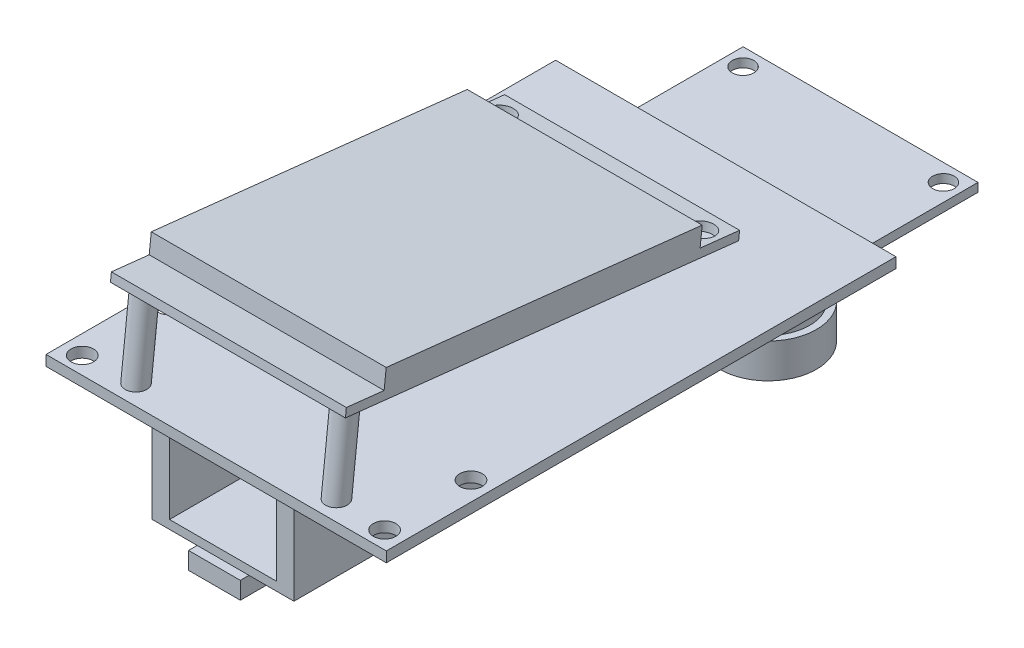
SolidWorks part; units mm, degrees
ref_plane "Front Plane" through (0, 0, 0) normal (0, 0, 1) x (1, 0, 0)
ref_plane "Top Plane" through (0, 0, 0) normal (0, 1, 0) x (1, 0, 0)
ref_plane "Right Plane" through (0, 0, 0) normal (1, 0, 0) x (0, 0, -1)
sketch "Sketch1" plane through (0, 0, 0) normal (0, 1, 0) x (1, 0, 0)
  line L0 (0, -46.1056) -> (0, 10.2781) construction
  line L1 (-25.019, 37.465) -> (25.019, 37.465)
  line L2 (-25.019, 37.465) -> (-25.019, -37.465)
  line L3 (-25.019, -37.465) -> (25.019, -37.465)
  line L4 (25.019, 37.465) -> (25.019, -37.465)
  circle A0 centre (22.225, -34.925) radius 1.651
  circle A1 centre (22.225, -22.225) radius 1.651
  circle A2 centre (-22.225, -34.925) radius 1.651
  circle A3 centre (-22.225, -22.225) radius 1.651
  point P4 (0, 37.465)
  point P6 (25.019, 0)
  point P12 (15.9217, -27.0723)
  point P16 (27.5932, -35.6314)
  dimension "D4" = 3.302
  dimension "D1" = 50.038
  dimension "D2" = 74.93
  dimension "D3" = 2.54
  dimension "D5" = 12.7
  dimension "D6" = 22.225
extrude "Boss-Extrude1" add sketch "Sketch1" along normal blind 1.524
sketch "Sketch2" plane through (0, 0, 0) normal (1, 0, 0) x (0, 0, -1)
  line L0 (22.0864, 7.366) -> (-35.732, 13.716)
  line L1 (22.0864, 7.366) -> (22.225, 8.6284)
  line L2 (-35.732, 13.716) -> (-35.5933, 14.9784)
  line L3 (22.225, 8.6284) -> (-35.5933, 14.9784)
  line L4 (37.465, 1.524) -> (37.465, 0) construction
  line L5 (-37.465, 1.524) -> (37.465, 1.524) construction
  line L6 (-30.0387, 14.3684) -> (16.4179, 9.2662)
  line L7 (-30.0387, 14.3684) -> (-29.7337, 17.1457)
  line L8 (16.4179, 9.2662) -> (16.7229, 12.0435)
  line L9 (-29.7337, 17.1457) -> (16.7229, 12.0435)
  dimension "D1" = 1.27
  dimension "D2" = 58.166
  dimension "D3" = 15.24
  dimension "D4" = 5.842
  dimension "D5" = 12.192
  dimension "D6" = 2.794
  dimension "D7" = 46.736
  dimension "D8" = 5.842
extrude "Boss-Extrude2" add sketch "Sketch2" along normal mid plane 34.544 separate body contours L9 L7 L3 L8 | L1 L3 L2 L0 region at (0, 11.1722, 6.7535) region at (0, 13.2059, 6.6579)
sketch "Sketch3" plane through (0, 10.9374, -1.2012) normal (0, 0.994, -0.1092) x (1, 0, 0)
  line L0 (-17.272, 21.1502) -> (-17.272, 15.3082) construction
  line L2 (17.272, 21.1502) -> (-17.272, 21.1502) construction
  line L3 (0, -9.4301) -> (0, 9.4301) construction
  circle A0 centre (-14.732, 18.1022) radius 1.778
  circle A2 centre (14.732, 18.1022) radius 1.778
  point P2 (0, 0)
  point P4 (0, 0)
  point P8 (-14.8989, 21.1502)
  dimension "D1" = 3.556
  dimension "D2" = 2.54
  dimension "D3" = 3.048
extrude "Cut-Extrude2" cut sketch "Sketch3" against normal up to next (1.27 mm away) contours A2 | A0 region at (14.732, 8.9612, -19.1952)
sketch "Sketch4" plane through (0, 9.675, -1.0626) normal (0, -0.994, 0.1092) x (1, 0, 0)
  line L0 (0.889, -19.3722) -> (-0.889, -19.3722) construction
  line L1 (17.272, -21.1502) -> (-17.272, -21.1502) construction
  line L2 (17.272, 31.4278) -> (17.272, 37.0158) construction
  line L4 (17.272, 37.0158) -> (-17.272, 37.0158) construction
  line L5 (0, -9.4301) -> (0, 9.4301) construction
  circle A0 centre (-0.889, -19.3722) radius 0.254
  circle A1 centre (0.889, -19.3722) radius 0.254
  circle A2 centre (-2.667, -19.3722) radius 0.254
  circle A3 centre (-4.445, -19.3722) radius 0.254
  circle A4 centre (-6.223, -19.3722) radius 0.254
  circle A5 centre (2.667, -19.3722) radius 0.254
  circle A6 centre (4.445, -19.3722) radius 0.254
  circle A7 centre (6.223, -19.3722) radius 0.254
  circle A8 centre (14.732, 34.4758) radius 1.5875
  circle A10 centre (-14.732, 34.4758) radius 1.5875
  point P8 (0, -19.3722)
  point P24 (0, 0)
  point P26 (14.0296, 37.0158)
  dimension "D1" = 0.508
  dimension "D2" = 0.508
  dimension "D7" = 3.175
  dimension "D3" = 1.778
  dimension "D4" = 1.778
  dimension "D8" = 2.54
  dimension "D9" = 2.54
  dimension "D5" = 4
  dimension "D6" = 4
extrude "Boss-Extrude3" add sketch "Sketch4" along normal up to next
sketch "Sketch5" plane through (0, 0, 0) normal (0, -1, 0) x (1, 0, 0)
  line L1 (10.414, 36.449) -> (7.874, 36.449)
  line L2 (10.414, 36.449) -> (10.414, -14.351)
  line L3 (10.414, -14.351) -> (7.874, -14.351)
  line L4 (7.874, 36.449) -> (7.874, -14.351)
  line L5 (-25.019, 37.465) -> (25.019, 37.465) construction
  line L6 (0, -9.4301) -> (0, 9.4301) construction
  line L7 (-10.414, -14.351) -> (-7.874, -14.351)
  line L8 (-7.874, 36.449) -> (-7.874, -14.351)
  line L9 (-10.414, 36.449) -> (-7.874, 36.449)
  line L10 (-10.414, 36.449) -> (-10.414, -14.351)
  point P4 (8.8726, -5.1163)
  dimension "D1" = 2.54
  dimension "D2" = 50.8
  dimension "D3" = 1.016
  dimension "D4" = 10.414
extrude "Boss-Extrude4" add sketch "Sketch5" along normal blind 11.43
sketch "Sketch6" plane through (0, -11.43, 0) normal (0, -1, 0) x (1, 0, 0)
  line L0 (-10.414, 36.449) -> (-10.414, -14.351) construction
  line L1 (-10.414, 36.449) -> (10.414, 36.449)
  line L2 (-10.414, 36.449) -> (-10.414, -14.351)
  line L3 (-10.414, -14.351) -> (10.414, -14.351)
  line L4 (10.414, 36.449) -> (10.414, -14.351)
  line L5 (-7.874, 36.449) -> (-10.414, 36.449) construction
extrude "Boss-Extrude5" add sketch "Sketch6" along normal blind 1.27
sketch "Sketch7" plane through (0, -12.7, 0) normal (0, -1, 0) x (1, 0, 0)
  line L1 (10.414, 36.449) -> (-10.414, 36.449) construction
  line L4 (-10.414, 36.449) -> (-10.414, -14.351) construction
  line L5 (0, -16.4151) -> (0, 16.4151) construction
  line L7 (3.81, 31.369) -> (-3.81, 31.369)
  line L8 (3.81, 31.369) -> (3.81, 37.719)
  line L9 (3.81, 37.719) -> (-3.81, 37.719)
  line L10 (-3.81, 31.369) -> (-3.81, 37.719)
  circle A0 centre (-9.144, 35.179) radius 0.889
  circle A1 centre (-9.144, 32.639) radius 0.889
  circle A2 centre (-9.144, 30.099) radius 0.889
  circle A3 centre (-9.144, 27.559) radius 0.889
  circle A4 centre (-9.144, 25.019) radius 0.889
  circle A5 centre (-9.144, 22.479) radius 0.889
  circle A6 centre (-9.144, 19.939) radius 0.889
  circle A7 centre (-9.144, 17.399) radius 0.889
  circle A8 centre (-9.144, 14.859) radius 0.889
  circle A9 centre (-9.144, 12.319) radius 0.889
  circle A10 centre (-9.144, 9.779) radius 0.889
  circle A11 centre (-9.144, 7.239) radius 0.889
  circle A12 centre (-9.144, 4.699) radius 0.889
  circle A13 centre (-9.144, 2.159) radius 0.889
  circle A14 centre (-9.144, -0.381) radius 0.889
  circle A15 centre (-9.144, -2.921) radius 0.889
  circle A16 centre (-9.144, -5.461) radius 0.889
  circle A17 centre (-9.144, -8.001) radius 0.889
  circle A18 centre (-9.144, -10.541) radius 0.889
  circle A19 centre (-9.144, -13.081) radius 0.889
  circle A20 centre (9.144, -13.081) radius 0.889
  circle A21 centre (9.144, -10.541) radius 0.889
  circle A22 centre (9.144, -8.001) radius 0.889
  circle A23 centre (9.144, -5.461) radius 0.889
  circle A24 centre (9.144, -2.921) radius 0.889
  circle A25 centre (9.144, -0.381) radius 0.889
  circle A26 centre (9.144, 2.159) radius 0.889
  circle A27 centre (9.144, 4.699) radius 0.889
  circle A28 centre (9.144, 7.239) radius 0.889
  circle A29 centre (9.144, 9.779) radius 0.889
  circle A30 centre (9.144, 12.319) radius 0.889
  circle A31 centre (9.144, 14.859) radius 0.889
  circle A32 centre (9.144, 17.399) radius 0.889
  circle A33 centre (9.144, 19.939) radius 0.889
  circle A34 centre (9.144, 22.479) radius 0.889
  circle A35 centre (9.144, 25.019) radius 0.889
  circle A36 centre (9.144, 27.559) radius 0.889
  circle A37 centre (9.144, 30.099) radius 0.889
  circle A38 centre (9.144, 32.639) radius 0.889
  circle A39 centre (9.144, 35.179) radius 0.889
  point P90 (0, 31.369)
  dimension "D1" = 1.778
  dimension "D2" = 1.27
  dimension "D3" = 1.27
  dimension "D5" = 5.08
  dimension "D6" = 6.35
  dimension "D7" = 7.62
  dimension "D4" = 20
extrude "Boss-Extrude6" add sketch "Sketch7" along normal blind 0.635 draft 45 contours A1 | A2 | A4 | A5 | A6 | A8 | A12 | A13 | A17 | A18 | A19 | A21 | A24 | A26 | A27 | A28 | A32 | A33 | A39 | A0 | A3 | A7 | A9 | A10 | A11 | A14 | A15 | A16 | A20 | A22 | A23 | A25 | A29 | A30 | A31 | A34 | A35 | A36 | A37 | A38 region at (-9.144, -12.7, 32.639) region at (-9.144, -12.7, 30.099) region at (-9.144, -12.7, 25.019) region at (-9.144, -12.7, 22.479) region at (-9.144, -12.7, 19.939) region at (-9.144, -12.7, 14.859) region at (-9.144, -12.7, 4.699) region at (-9.144, -12.7, 2.159) region at (-9.144, -12.7, -8.001) region at (-9.144, -12.7, -10.541) region at (-9.144, -12.7, -13.081) region at (9.144, -12.7, -10.541) region at (9.144, -12.7, -2.921) region at (9.144, -12.7, 2.159) region at (9.144, -12.7, 4.699) region at (9.144, -12.7, 7.239) region at (9.144, -12.7, 17.399) region at (9.144, -12.7, 19.939)
extrude "Boss-Extrude7" add sketch "Sketch7<3>" along normal blind 2.54 contours L9 L10 L7 L8
sketch "Sketch7<3>" plane through (0, -12.7, 0) normal (0, -1, 0) x (1, 0, 0) same geometry as "Sketch7"
sketch "Sketch9" plane through (0, 0, 0) normal (0, -1, 0) x (1, 0, 0)
  line L0 (25.019, -37.465) -> (-25.019, -37.465) construction
  line L1 (17.272, -22.225) -> (-17.272, -22.225)
  line L2 (17.272, -22.225) -> (17.272, -57.277)
  line L3 (17.272, -57.277) -> (-17.272, -57.277)
  line L4 (-17.272, -22.225) -> (-17.272, -57.277)
  point P6 (0, -37.465)
  point P7 (0, -57.277)
  dimension "D1" = 35.052
  dimension "D2" = 34.544
  dimension "D3" = 15.24
extrude "Boss-Extrude8" add sketch "Sketch9" along normal blind 1.27 from offset 2.794 separate body
sketch "Sketch10" plane through (0, -4.064, 0) normal (0, -1, 0) x (1, 0, 0)
  line L0 (0, -57.277) -> (0, -22.225) construction
  line L1 (-8.255, -51.943) -> (8.255, -51.943)
  line L2 (-8.255, -51.943) -> (-8.255, -35.433)
  line L3 (-8.255, -35.433) -> (8.255, -35.433)
  line L4 (8.255, -51.943) -> (8.255, -35.433)
  line L5 (-17.272, -57.277) -> (17.272, -57.277) construction
  line L6 (17.272, -22.225) -> (-17.272, -22.225) construction
  line L7 (-9.779, -43.688) -> (9.779, -43.688) construction
  line L8 (-9.779, -41.656) -> (-8.255, -41.656)
  line L9 (-9.779, -45.72) -> (-8.255, -45.72)
  line L10 (9.779, -41.656) -> (8.255, -41.656)
  line L11 (9.779, -45.72) -> (8.255, -45.72)
  arc A0 (-9.779, -41.656) -> (-9.779, -45.72) centre (-9.779, -43.688) ccw
  arc A1 (9.779, -45.72) -> (9.779, -41.656) centre (9.779, -43.688) ccw
  point P10 (0, -35.433)
  point P13 (0, -43.688)
  point P14 (-8.255, -43.688)
  dimension "D4" = 4.064
  dimension "D5" = 1.524
  dimension "D1" = 16.51
  dimension "D2" = 16.51
  dimension "D3" = 5.334
extrude "Boss-Extrude9" add sketch "Sketch10" along normal blind 7.62 contours L8 A0 L9 L2 | L1 L4 L3 L2 | L11 A1 L10 L4 region at (0, -4.064, -43.688) region at (-9.8479, -4.064, -43.688) region at (9.8479, -4.064, -43.688)
sketch "Sketch11" plane through (0, -11.684, 0) normal (0, -1, 0) x (1, 0, 0)
  line L0 (-8.255, -51.943) -> (8.255, -35.433) construction
  circle A0 centre (0, -43.688) radius 7.366
  dimension "D1" = 14.732
extrude "Boss-Extrude10" add sketch "Sketch11" along normal blind 5.588
sketch "Sketch12" plane through (0, -17.272, 0) normal (0, -1, 0) x (1, 0, 0)
  circle A2 centre (0, -43.688) radius 6.096
  circle A3 centre (0, -43.688) radius 6.096
  dimension "D1" = 1.27
extrude "Boss-Extrude11" add sketch "Sketch12" along normal blind 2.54
sketch "Sketch13" plane through (0, -19.812, 0) normal (0, -1, 0) x (1, 0, 0)
  circle A2 centre (0, -43.688) radius 7.112
  circle A3 centre (0, -43.688) radius 7.112
  dimension "D1" = 1.016
extrude "Boss-Extrude12" add sketch "Sketch13" along normal blind 5.08
sketch "Sketch14" plane through (0, 0, 0) normal (1, 0, 0) x (0, 0, -1)
  line L0 (43.688, -19.812) -> (43.688, -27.5839) construction
  line L1 (50.8, -19.812) -> (36.576, -19.812) construction
  line L2 (50.5445, -24.892) -> (49.4447, -24.257)
  line L3 (36.576, -24.892) -> (50.8, -24.892) construction
  line L4 (43.688, -24.765) -> (46.5888, -24.765) construction
  line L5 (46.5888, -24.765) -> (49.4447, -24.257) construction
  line L6 (50.8, -24.892) -> (50.8, -19.812) construction
  line L7 (43.688, -24.765) -> (43.688, -27.265)
  line L8 (43.688, -27.265) -> (50.5445, -27.265)
  line L9 (50.5445, -27.265) -> (50.5445, -24.892)
  spline S0 degree 2 poles (43.688, -24.765) (46.5888, -24.765) (49.4447, -24.257) knots 0 0 0 1 1 1
  dimension "D1" = 0.2555
  dimension "D2" = 30
  dimension "D3" = 1.27
  dimension "D4" = 0.127
revolve "Cut-Revolve1" cut sketch "Sketch14" angle 360 about L0
sketch "Sketch15" plane through (0, -4.064, 0) normal (0, -1, 0) x (1, 0, 0)
  line L0 (0, -22.225) -> (0, -57.277) construction
  line L1 (17.272, -22.225) -> (-17.272, -22.225) construction
  line L2 (-17.272, -57.277) -> (17.272, -57.277) construction
  line L3 (-17.272, -39.751) -> (17.272, -39.751) construction
  line L4 (-17.272, -22.225) -> (-17.272, -57.277) construction
  line L5 (17.272, -57.277) -> (17.272, -22.225) construction
  circle A0 centre (-14.732, -24.765) radius 1.5875
  circle A1 centre (14.732, -24.765) radius 1.5875
  circle A2 centre (14.732, -54.737) radius 1.5875
  circle A3 centre (-14.732, -54.737) radius 1.5875
  dimension "D2" = 3.175
  dimension "D1" = 2.54
  dimension "D3" = 2.54
extrude "Cut-Extrude3" cut sketch "Sketch15" against normal up to next (1.27 mm away)
sketch "Sketch16" plane through (0, -4.064, 0) normal (0, -1, 0) x (1, 0, 0)
  line L0 (0, -22.225) -> (0, -39.6271) construction
  line L1 (17.272, -22.225) -> (-17.272, -22.225) construction
  circle A0 centre (11.43, -27.305) radius 0.889
  circle A1 centre (9.144, -13.081) radius 0.889 construction
  circle A2 centre (8.89, -27.305) radius 0.889
  circle A3 centre (6.35, -27.305) radius 0.889
  circle A4 centre (3.81, -27.305) radius 0.889
  circle A5 centre (1.27, -27.305) radius 0.889
  circle A6 centre (-1.27, -27.305) radius 0.889
  circle A7 centre (-3.81, -27.305) radius 0.889
  circle A8 centre (-6.35, -27.305) radius 0.889
  circle A9 centre (-8.89, -27.305) radius 0.889
  circle A10 centre (-11.43, -27.305) radius 0.889
  circle A11 centre (8.89, -29.845) radius 0.889
  circle A12 centre (6.35, -29.845) radius 0.889
  circle A13 centre (3.81, -29.845) radius 0.889
  circle A14 centre (1.27, -29.845) radius 0.889
  circle A15 centre (-1.27, -29.845) radius 0.889
  circle A16 centre (-3.81, -29.845) radius 0.889
  circle A17 centre (-6.35, -29.845) radius 0.889
  circle A18 centre (-8.89, -29.845) radius 0.889
  circle A19 centre (-11.43, -29.845) radius 0.889
  circle A20 centre (11.43, -29.845) radius 0.889
  dimension "D1" = 11.43
  dimension "D2" = 5.08
  dimension "D3" = 10
  dimension "D4" = 2
extrude "Boss-Extrude13" add sketch "Sketch16" against normal up to surface (4.064 mm away) up to face at (9.144, 0, 11.049)
extrude "Boss-Extrude14" add sketch "Sketch16<2>" along normal blind 0.635 draft 45 contours A19 | A18 | A9 | A8 | A17 | A16 | A7 | A6 | A15 | A14 | A5 | A13 | A4 | A12 | A3 | A11 | A2 | A20 | A0 | A10 region at (11.43, -4.064, -27.305) region at (8.89, -4.064, -27.305) region at (6.35, -4.064, -27.305) region at (3.81, -4.064, -27.305) region at (1.27, -4.064, -27.305) region at (-1.27, -4.064, -27.305) region at (-3.81, -4.064, -27.305) region at (-6.35, -4.064, -27.305) region at (-8.89, -4.064, -27.305) region at (8.89, -4.064, -29.845) region at (6.35, -4.064, -29.845) region at (3.81, -4.064, -29.845) region at (1.27, -4.064, -29.845) region at (-1.27, -4.064, -29.845) region at (-3.81, -4.064, -29.845) region at (-6.35, -4.064, -29.845) region at (-8.89, -4.064, -29.845) region at (-11.43, -4.064, -29.845) region at (11.43, -4.064, -29.845)
sketch "Sketch16<2>" plane through (0, -4.064, 0) normal (0, -1, 0) x (1, 0, 0) same geometry as "Sketch16"
